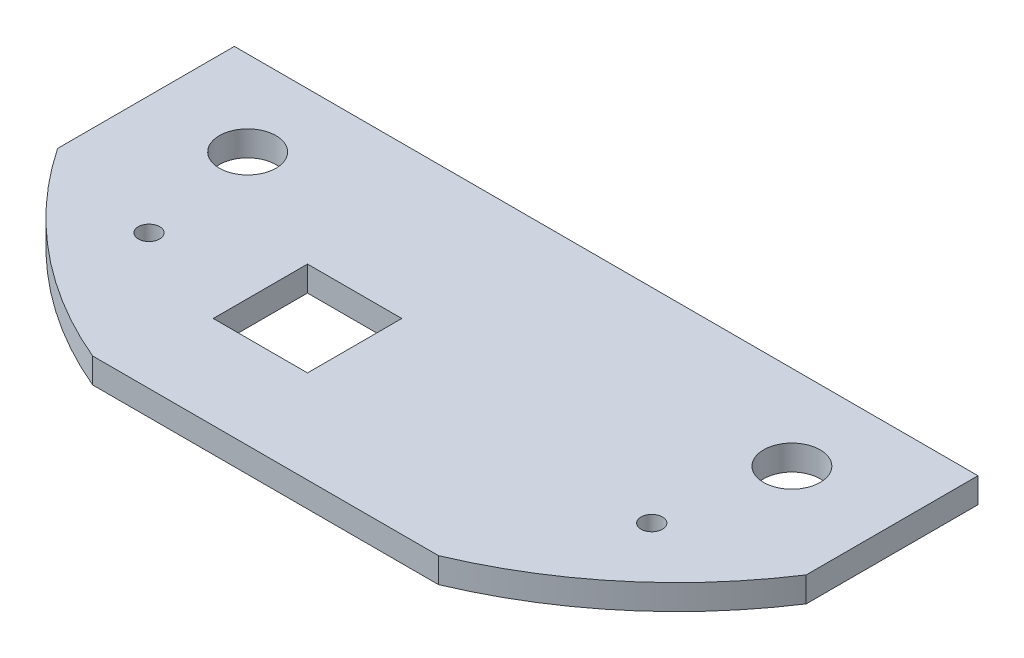
SolidWorks part; units mm, degrees
ref_plane "Plan de face" through (0, 0, 0) normal (0, 0, 1) x (1, 0, 0)
ref_plane "Plan de dessus" through (0, 0, 0) normal (0, 1, 0) x (1, 0, 0)
ref_plane "Plan de droite" through (0, 0, 0) normal (1, 0, 0) x (0, 0, -1)
sketch "Esquisse1" plane through (0, 0, 0) normal (0, 1, 0) x (1, 0, 0)
  line L0 (-58.9016, 6.7115) -> (-58.9016, 32.4862)
  line L1 (31.5, 12.5) -> (-31.5, 12.5)
  line L2 (31.5, 12.5) -> (31.5, -12.5)
  line L3 (31.5, -12.5) -> (-31.5, -12.5)
  line L4 (-31.5, 12.5) -> (-31.5, -12.5)
  line L5 (31.5, 12.5) -> (-31.5, -12.5) construction
  line L6 (31.5, -12.5) -> (-31.5, 12.5) construction
  line L7 (-58.9016, 32.4862) -> (59.4279, 32.4862)
  line L8 (59.4279, 32.4862) -> (59.4279, 7.4872)
  line L9 (0, 0) -> (0, 47.2436) construction
  line L10 (-58.9016, 6.7115) -> (0, 47.2436) construction
  line L11 (0, 47.2436) -> (59.4279, 7.4872) construction
  line L12 (-43.3, 22.2414) -> (43.3, 22.2414) construction
  line L13 (43.3, 22.2414) -> (0, 47.2436) construction
  line L14 (0, 47.2436) -> (-43.3, 22.2414) construction
  line L15 (-58.9016, 6.7115) -> (-58.9016, -21.4508)
  line L16 (-58.9016, -21.4508) -> (59.4279, -21.4508)
  line L17 (59.4279, -21.4508) -> (59.4279, 7.4872)
  point P8 (43.3, 22.2414)
  point P13 (0, 47.2436)
  point P14 (-43.3, 22.2414)
  point P16 (0, 22.2414)
  dimension "D3" = 71.5
  dimension "D1" = 25
  dimension "D2" = 63
  dimension "D4" = 50
  dimension "D5" = 86.6
extrude "Boss.-Extru.1" add sketch "Esquisse1" along normal blind 4
hole_wizard "Dégagement M81" positions "Esquisse2" profile "Esquisse4" hole size "M8" standard "DIN" end condition through all
sketch "Esquisse2" plane through (0, 4, 0) normal (0, 1, 0) x (1, 0, 0)
  line L0 (-43.3, 19) -> (0, 0) construction
  line L1 (0, 0) -> (43.3, 19) construction
  line L2 (43.3, 19) -> (-43.3, 19) construction
  point P0 (-43.3, 19)
  point P2 (43.3, 19)
  dimension "D1" = 86.6
  dimension "D2" = 19
sketch "Esquisse4" plane through (-43.3, 4, -19) normal (1, 0, 0) x (0, 0, 1)
  line L0 (0, 0) -> (0, 4)
  line L1 (0, 4) -> (4.5, 4)
  line L2 (4.5, 4) -> (4.5, 0)
  line L5 (4.5, 0) -> (0, 0)
  line L11 (0, -6.35) -> (0, 107.95) construction
  dimension "Diamètre du perçage jusqu'au prochain" = 9
  dimension "Profondeur du perçage jusqu'au prochain" = 4
sketch "Esquisse5" plane through (0, 4, 0) normal (0, 1, 0) x (1, 0, 0)
  line L0 (0, 44.0022) -> (0, 0) construction
  line L1 (-43.3, 19) -> (0, 44.0022) construction
  circle A0 centre (0, 44.0022) radius 71
  circle A1 centre (0, 44.0022) radius 96
  dimension "D1" = 25
  dimension "D3" = 142
  dimension "D2" = 50
extrude "Enlèv. mat.-Extru.1" cut sketch "Esquisse5" against normal through all
sketch "Esquisse6" plane through (0, 4, 0) normal (0, 1, 0) x (1, 0, 0)
  line L4 (31.5, -12.5) -> (31.5, 12.5) construction
  line L5 (-31.5, -12.5) -> (31.5, -12.5) construction
  line L6 (-31.5, 12.5) -> (-31.5, -12.5) construction
  line L7 (31.5, 12.5) -> (-31.5, 12.5) construction
  line L8 (31.5, -12.5) -> (31.5, 12.5)
  line L9 (-31.5, -12.5) -> (31.5, -12.5)
  line L10 (-31.5, 12.5) -> (-31.5, -12.5)
  line L11 (31.5, 12.5) -> (-31.5, 12.5)
extrude "Boss.-Extru.2" add sketch "Esquisse6" against normal up to surface (4 mm away) up to face at (-43.3, 0, -14.5)
sketch "Esquisse7" plane through (0, 4, 0) normal (0, 1, 0) x (1, 0, 0)
  line L1 (-23.0852, -6.6923) -> (-8.0852, -6.6923)
  line L2 (-23.0852, -6.6923) -> (-23.0852, 8.3077)
  line L3 (-23.0852, 8.3077) -> (-8.0852, 8.3077)
  line L4 (-8.0852, -6.6923) -> (-8.0852, 8.3077)
  line L5 (-23.0852, -6.6923) -> (-8.0852, 8.3077) construction
  line L6 (-23.0852, 8.3077) -> (-8.0852, -6.6923) construction
  point P0 (-15.5852, 0.8077)
  dimension "D1" = 15
extrude "Enlèv. mat.-Extru.2" cut sketch "Esquisse7" against normal through all
hole_wizard "Dégagement M31" positions "Esquisse8" profile "Esquisse9" hole size "M3" standard "DIN" end condition through all
sketch "Esquisse8" plane through (0, 4, 0) normal (0, 1, 0) x (1, 0, 0)
  point P0 (-40, 0)
  point P3 (40, 0)
sketch "Esquisse9" plane through (-40, 4, 0) normal (1, 0, 0) x (0, 0, 1)
  line L0 (0, 0) -> (0, 4)
  line L1 (0, 4) -> (1.7, 4)
  line L2 (1.7, 4) -> (1.7, 0)
  line L5 (1.7, 0) -> (0, 0)
  line L11 (0, -6.35) -> (0, 107.95) construction
  dimension "Diamètre du perçage jusqu'au prochain" = 3.4
  dimension "Profondeur du perçage jusqu'au prochain" = 4
